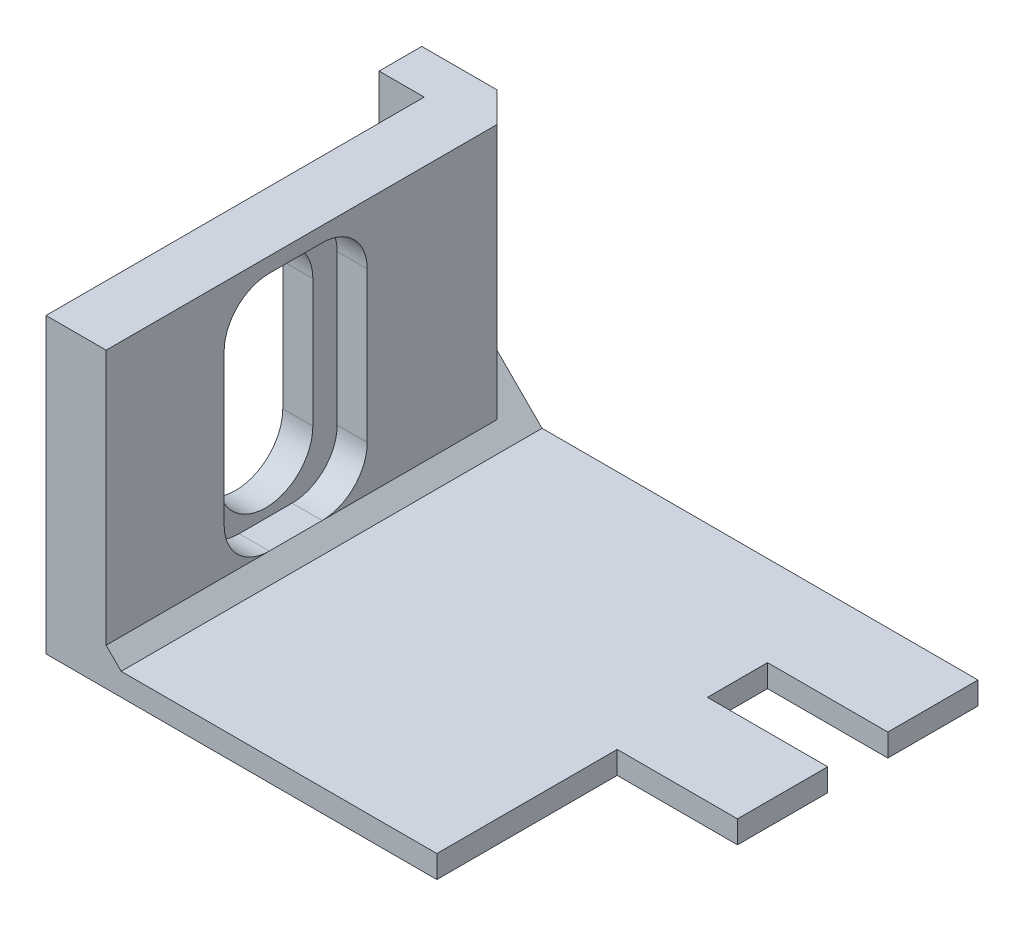
SolidWorks part; units mm, degrees
ref_plane "Front" through (0, 0, 0) normal (0, 0, 1) x (1, 0, 0)
ref_plane "Top" through (0, 0, 0) normal (0, 1, 0) x (1, 0, 0)
ref_plane "Right" through (0, 0, 0) normal (1, 0, 0) x (0, 0, -1)
sketch "Sketch1" plane through (0, 0, 0) normal (0, 1, 0) x (1, 0, 0)
  line L0 (0, -2.84) -> (0, 0)
  line L1 (0, 0) -> (37, 0)
  line L3 (29, -6) -> (37, -6)
  line L4 (37, 0) -> (37, -6)
  line L6 (29, -6) -> (29, -10)
  line L9 (29, -10) -> (37, -10)
  line L11 (29, -16) -> (37, -16)
  line L12 (37, -10) -> (37, -16)
  line L15 (3, -28) -> (29, -28)
  line L16 (29, -16) -> (29, -28)
  line L20 (0, -2.84) -> (3, -2.84)
  line L21 (3, -28) -> (3, -2.84)
  dimension "D1" = 6
  dimension "D2" = 6
  dimension "D3" = 4
  dimension "D4" = 3
  dimension "D5" = 2.84
  dimension "D6" = 28
  dimension "D7" = 37
  dimension "D8" = 8
  dimension "D9" = 8
extrude "Boss-Extrude1" add sketch "Sketch1" along normal blind 1.5
sketch "Sketch2" plane through (0, 1.5, 0) normal (0, 1, 0) x (1, 0, 0)
  line L18 (0, 0) -> (7, 0)
  line L19 (37, 0) -> (0, 0) construction
  line L20 (7, 0) -> (7, -28)
  line L21 (3, -28) -> (29, -28) construction
  line L22 (7, -28) -> (3, -28)
  line L23 (3, -28) -> (3, -2.84)
  line L24 (3, -2.84) -> (0, -2.84)
  line L25 (0, -2.84) -> (0, 0)
  dimension "D1" = 4
extrude "Boss-Extrude2" add sketch "Sketch2" along normal blind 18 and the other way blind 1
sketch "Sketch4" plane through (7, 0, 0) normal (1, 0, 0) x (0, 0, -1)
  line L0 (-15.39, 18.5) -> (-15.39, 2.5) construction
  line L4 (-17.15, 2.5) -> (-13.63, 2.5)
  line L5 (-20.15, 5.5) -> (-20.15, 15.5)
  line L8 (-17.15, 18.5) -> (-13.63, 18.5)
  line L9 (-10.63, 5.5) -> (-10.63, 15.5)
  line L10 (-28, 1.5) -> (-28, 19.5) construction
  line L11 (0, 19.5) -> (-28, 19.5) construction
  arc A4 (-20.15, 5.5) -> (-17.15, 2.5) centre (-17.15, 5.5) ccw
  arc A5 (-13.63, 2.5) -> (-10.63, 5.5) centre (-13.63, 5.5) ccw
  arc A6 (-13.63, 18.5) -> (-10.63, 15.5) centre (-13.63, 15.5) cw
  arc A7 (-20.15, 15.5) -> (-17.15, 18.5) centre (-17.15, 15.5) cw
  dimension "D3" = 3
  dimension "D1" = 12.61
  dimension "D2" = 9.52
  dimension "D4" = 10
  dimension "D5" = 4
extrude "Cut-Extrude2" cut sketch "Sketch4" against normal blind 2
sketch "Sketch5" plane through (5, 0, 0) normal (1, 0, 0) x (0, 0, -1)
  line L0 (-15.39, 14.75) -> (-15.39, 6.25) construction
  line L1 (-12.25, 14.75) -> (-12.25, 6.25)
  line L2 (-18.53, 14.75) -> (-18.53, 6.25)
  line L3 (0, 19.5) -> (-28, 19.5) construction
  line L5 (-28, 1.5) -> (-28, 19.5) construction
  arc A0 (-12.25, 14.75) -> (-18.53, 14.75) centre (-15.39, 14.75) ccw
  arc A1 (-18.53, 6.25) -> (-12.25, 6.25) centre (-15.39, 6.25) ccw
  point P2 (-15.39, 10.5)
  dimension "D1" = 6.28
  dimension "D2" = 12.61
  dimension "D3" = 8.5
  dimension "D4" = 4.75
extrude "Cut-Extrude3" cut sketch "Sketch5" against normal through all
chamfer "Chamfer1" distance 1 angle 45 1 edges at (7, 1.5, 14)
chamfer "Chamfer2" distance 2 angle 45 1 edges at (7, 11, 0)
